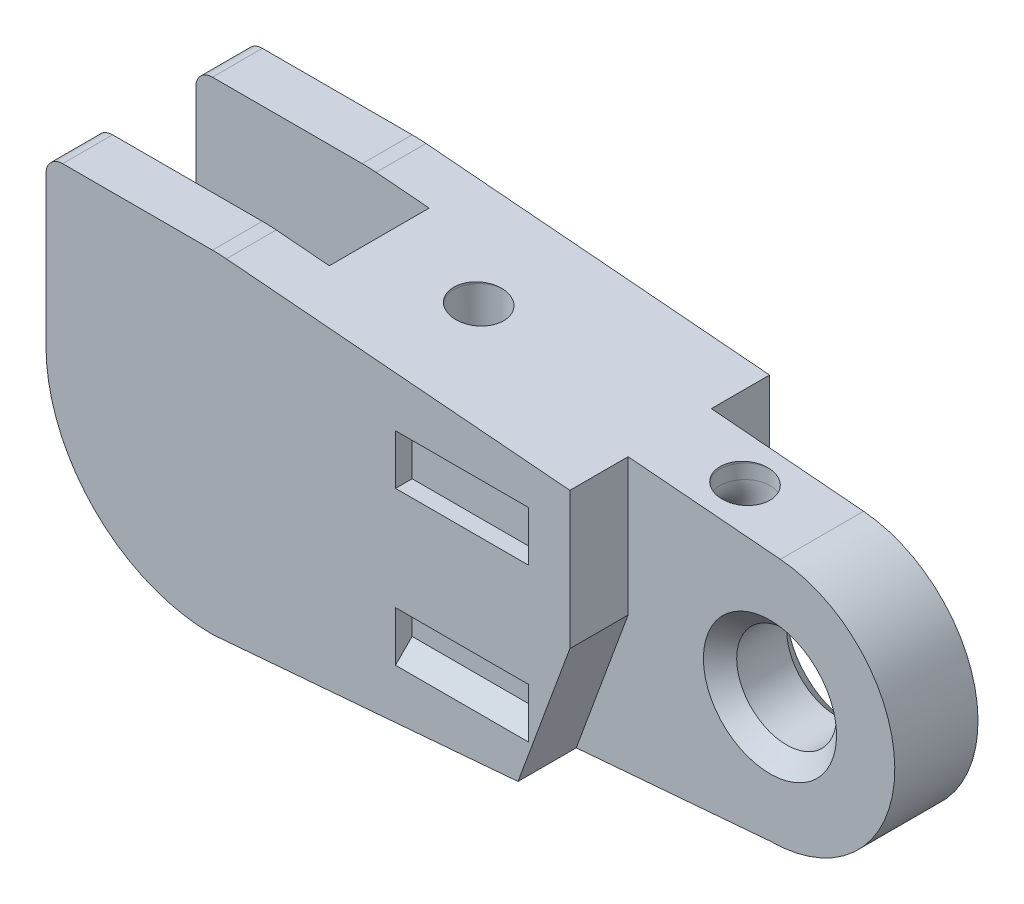
SolidWorks part; units mm, degrees
ref_plane "Front Plane" through (0, 0, 0) normal (0, 0, 1) x (1, 0, 0)
ref_plane "Top Plane" through (0, 0, 0) normal (0, 1, 0) x (1, 0, 0)
ref_plane "Right Plane" through (0, 0, 0) normal (1, 0, 0) x (0, 0, -1)
sketch "Sketch1" plane through (0, 0, 0) normal (0, 0, 1) x (1, 0, 0)
  line L0 (55, 0) -> (-55, 0) construction
  line L1 (0, -55) -> (0, 55) construction
  line L2 (-14.1667, 9.9652) -> (15.625, 7.4739)
  line L3 (-15, -10) -> (15, -7.5)
  line L4 (-15, 10) -> (-24, 10)
  line L5 (-25, 9) -> (-25, 0)
  arc A0 (-25, 0) -> (-15, 10) centre (-15, 0) ccw
  circle A1 centre (15, 0) radius 7.5
  circle A2 centre (-15, 0) radius 2.5
  circle A3 centre (15, 0) radius 3
  arc A4 (-24, 10) -> (-25, 9) centre (-24, 9) ccw
  dimension "D1" = 20
  dimension "D2" = 15
  dimension "D5" = 5
  dimension "D6" = 6
  dimension "D7" = 1
  dimension "D3" = 30
  dimension "D4" = 15
extrude "Boss-Extrude1" add sketch "Sketch1" along normal mid plane 12 contours A1 L2 A0 L3 region at (0.9606, 0.0273, 0)
extrude "Boss-Extrude2" add sketch "Sketch1<3>" along normal mid plane 12 contours A0 L3 A2 region at (-5.2912, 0.4024, 0)
sketch "Sketch1<3>" plane through (0, 0, 0) normal (0, 0, 1) x (1, 0, 0) same geometry as "Sketch1"
extrude "Boss-Extrude3" add sketch "Sketch1<5>" along normal mid plane 9 contours A1 A3 region at (20.3637, 4.9339, 0)
sketch "Sketch1<5>" plane through (0, 0, 0) normal (0, 0, 1) x (1, 0, 0) same geometry as "Sketch1"
extrude "Cut-Extrude2" cut sketch "Sketch1<6>" against normal mid plane 6 contours A0 L3 A2 region at (-5.2912, 0.4024, 0)
sketch "Sketch1<6>" plane through (0, 0, 0) normal (0, 0, 1) x (1, 0, 0) same geometry as "Sketch1"
sketch "Sketch2" plane through (0, 0, 0) normal (0, 0, 1) x (1, 0, 0)
  line L0 (-4.5, 0) -> (-4.5, -10.5)
  line L1 (-4.5, -10.5) -> (-15, -10.5)
  line L2 (6.4759, 0) -> (3, -9.4488)
  line L3 (3, -9.4488) -> (15, -9.4488)
  line L4 (15, -9.4488) -> (15, -8)
  line L5 (6.4759, 0) -> (16.0501, 0)
  line L6 (6.6, 0) -> (-6.6, 0) construction
  line L7 (6.4759, 0) -> (6.4759, 8.8777)
  line L8 (6.4759, 8.8777) -> (15, 8)
  arc A0 (-4.5, 0) -> (-15, -10.5) centre (-15, 0) ccw
  arc A1 (15, -8) -> (15, 8) centre (15, 0) ccw
  dimension "D1" = 21
  dimension "D2" = 16
  dimension "D3" = 12
extrude "Cut-Extrude3" cut sketch "Sketch2" against normal mid plane 6 contours L0 A0 L1 region at (-14.4786, -0.5214, 0)
extrude "Cut-Extrude4" cut sketch "Sketch2<3>" along normal blind 7.5 from offset 10 contours A1 region at (13.245, -0.6687, 0) offset against normal yes
sketch "Sketch2<3>" plane through (0, 0, 0) normal (0, 0, 1) x (1, 0, 0) same geometry as "Sketch2"
mirror "Mirror1" about plane through (0, 0, 0) normal (0, 0, 1) of "Cut-Extrude4"
sketch "Sketch3" plane through (0, 0, 0) normal (0, 0, 1) x (1, 0, 0)
  line L0 (-5, 9.1987) -> (-5, 7)
  line L2 (-2, 4) -> (8, 4)
  line L3 (11, 7) -> (11, 7.8607)
  line L4 (-14.1667, 9.9652) -> (6.4759, 8.239) construction
  line L5 (-5, 9.1987) -> (-5, 11.3767)
  line L7 (11, 7.8607) -> (11, 10.9782)
  line L8 (0, -6.6) -> (0, 6.6) construction
  line L9 (6.6, 0) -> (-6.6, 0) construction
  arc A2 (11, 7) -> (8, 4) centre (8, 7) cw
  arc A3 (-2, 4) -> (-5, 7) centre (-2, 7) cw
  point P24 (11, 4)
  point P27 (-5, 4)
  dimension "D1" = 16
  dimension "D2" = 5
  dimension "D3" = 4
sweep "Cut-Sweep5" cut path "Sketch3" circular profile diameter 3 parameters "D3"=3
mirror "Mirror2" about plane through (0, 0, 0) normal (0, 1, 0) of "Cut-Sweep5"
extrude "Boss-Extrude4" add sketch "Sketch1<7>" along normal mid plane 12 contours A2 region at (-15, 0, 0)
sketch "Sketch1<7>" plane through (0, 0, 0) normal (0, 0, 1) x (1, 0, 0) same geometry as "Sketch1"
chamfer "Chamfer1" distance 1 angle 45 4 edges at (18, 0, -2.5) (12, 0, 2.5) (-12.5, 0, 3) (-12.5, 0, -3)
sketch "Sketch139" plane through (0, 0, 0) normal (1, 0, 0) x (0, 0, -1)
  line L0 (6, 9.1021) -> (6, 6.1021)
  line L1 (6, 9.9652) -> (6, 8.239) construction
  line L2 (6, 8.239) -> (6, 0) construction
  line L3 (6, 6.1021) -> (5, 5.1021)
  line L4 (5, 5.1021) -> (5, 3.1021)
  line L5 (5, 3.1021) -> (7.605, 3.1021)
  line L6 (7.605, 3.1021) -> (7.605, 9.1021)
  line L7 (7.605, 9.1021) -> (6, 9.1021)
  dimension "D1" = 3
  dimension "D2" = 1
  dimension "D3" = 1
  dimension "D4" = 2
extrude "Cut-Extrude5" cut sketch "Sketch139" against normal mid plane 8
mirror "Mirror3" about plane through (0, 0, 0) normal (0, 1, 0) of "Cut-Extrude5"
mirror "Mirror4" about plane through (0, 0, 0) normal (0, 0, 1) of "Mirror3"
